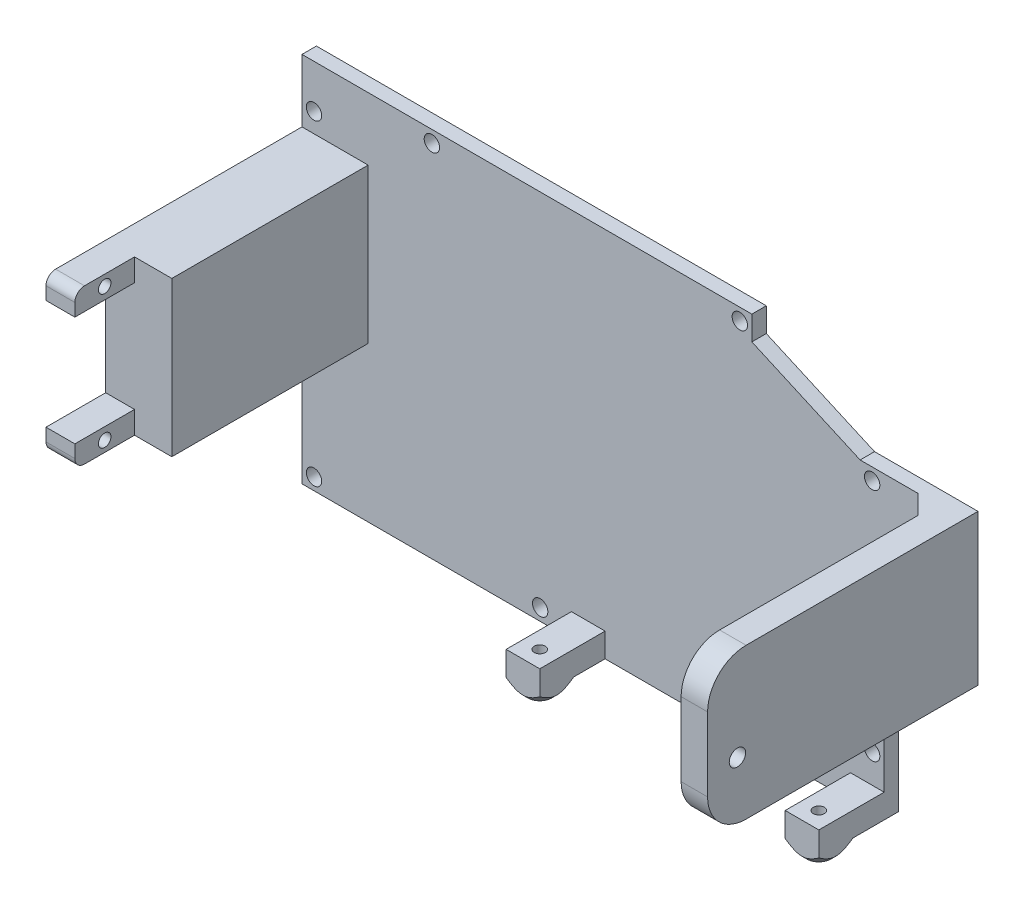
SolidWorks part; units mm, degrees
material "Nylon 101 70%"
ref_plane "Front Plane" through (0, 0, 0) normal (0, 0, 1) x (1, 0, 0)
ref_plane "Top Plane" through (0, 0, 0) normal (0, 1, 0) x (1, 0, 0)
ref_plane "Right Plane" through (0, 0, 0) normal (1, 0, 0) x (0, 0, -1)
sketch "Sketch19" plane through (0, 0, 0) normal (0, 0, 1) x (1, 0, 0)
  line L10 (-54.5, -38) -> (-54.5, 29.3)
  line L11 (56.5, -38) -> (-54.5, -38)
  line L12 (56.5, 19.3) -> (56.5, -38)
  line L13 (61.5, 19.3) -> (56.5, 19.3)
  line L14 (61.5, -43) -> (61.5, 19.3)
  line L15 (-59.5, -43) -> (61.5, -43)
  line L16 (-59.5, 34.3) -> (-59.5, -43)
  line L17 (34, 34.3) -> (-59.5, 34.3)
  line L18 (34, 29.3) -> (34, 34.3)
  line L19 (-54.5, 29.3) -> (34, 29.3)
  line L20 (-54.5, -38) -> (-54.5, 29.3) construction
  line L21 (56.5, -38) -> (-54.5, -38) construction
  line L22 (56.5, 19.3) -> (56.5, -38) construction
  line L23 (61.5, 19.3) -> (56.5, 19.3)
  line L24 (61.5, -43) -> (61.5, 19.3)
  line L25 (-59.5, -43) -> (61.5, -43)
  line L26 (-59.5, 34.3) -> (-59.5, -43)
  line L27 (34, 34.3) -> (-59.5, 34.3)
  line L28 (34, 29.3) -> (34, 34.3)
  line L29 (-54.5, 29.3) -> (34, 29.3) construction
  line L40 (34, 29.3) -> (56.5, 19.3)
  dimension "D1" = 0
extrude "Base" add sketch "Sketch19" along normal blind 3
ref_plane "Top" through (0, 0, 3) normal (0, 0, 1) x (1, 0, 0)
sketch "Sketch20" plane through (0, 0, 0) normal (0, 0, 1) x (1, 0, 0)
  line L0 (-55.6482, 16.7928) -> (-55.6482, 21.05) construction
  line L1 (-55.4482, -7.9314) -> (-55.4482, -9.2765) construction
  line L2 (-55.8482, -6.2) -> (-73.6482, -6.2) construction
  line L3 (-55.8482, -6.2) -> (-73.6482, -6.2) construction
  line L4 (-55.6482, 16.7928) -> (-55.6482, 21.05) construction
  line L5 (-55.4482, -7.9314) -> (-55.4482, -9.2765) construction
  line L6 (-55.8482, 16.6) -> (-73.6482, 16.6) construction
  line L7 (-55.8482, 16.6) -> (-73.6482, 16.6) construction
  line L8 (-55.6482, -10.65) -> (-55.6482, -6.3928) construction
  line L9 (-55.4482, 21.25) -> (-53.2982, 21.25) construction
  line L10 (-55.4482, 18.2177) -> (-55.4482, 19.799) construction
  line L11 (-55.4482, 18.2177) -> (-55.4482, 19.799) construction
  line L12 (-53.2982, -10.85) -> (-55.4482, -10.85) construction
  line L13 (-53.2982, -10.85) -> (-55.4482, -10.85)
  line L14 (-55.4482, 21.25) -> (-53.2982, 21.25)
  line L15 (-51.3482, -6.2) -> (-52.8982, -6.2) construction
  line L16 (-51.3482, -6.2) -> (-52.8982, -6.2) construction
  line L17 (-52.8982, 16.6) -> (-51.3482, 16.6) construction
  line L18 (-52.8982, 16.6) -> (-51.3482, 16.6) construction
  line L19 (-45.7482, 8.6095) -> (-50.9482, 8.6095) construction
  line L20 (-45.7482, 8.6095) -> (-50.9482, 8.6095) construction
  line L21 (-50.9482, -6.2) -> (-45.3482, -6.2) construction
  line L22 (-50.9482, -6.2) -> (-45.3482, -6.2) construction
  line L23 (-53.2982, 21.25) -> (-45.7482, 21.25)
  line L24 (-45.7482, 21.25) -> (-45.7482, 8.6095)
  line L25 (-45.7482, 8.6095) -> (-45.7482, -10.85)
  line L26 (-45.7482, -10.85) -> (-53.2982, -10.85)
  line L27 (-55.4482, 21.25) -> (-59.5, 21.25)
  line L28 (-59.5, 34.3) -> (-59.5, -43) construction
  line L29 (-59.5, 21.25) -> (-59.5, -10.85)
  line L30 (-59.5, -10.85) -> (-55.4482, -10.85)
  line L31 (-55.6482, -10.65) -> (-55.6482, -6.3928) construction
extrude "Servo support" add sketch "Sketch20" along normal up to surface (43.8 mm away)
sketch "Sketch21" plane through (0, 0, 43.8) normal (0, 0, 1) x (1, 0, 0)
  line L0 (-53.5, -6.3928) -> (-53.5, -10.65) construction
  line L2 (-53.5, -6.2) -> (-53.5, -10.85)
  line L4 (-55.8482, -6.2) -> (-73.6482, -6.2) construction
  line L5 (-53.5, -6.2) -> (-59.5, -6.2)
  line L6 (-55.8482, 16.6) -> (-73.6482, 16.6) construction
  line L7 (-53.5, 16.6) -> (-59.5, 16.6)
  line L8 (-59.5, -10.85) -> (-55.4482, -10.85) construction
  line L9 (-59.5, -10.85) -> (-53.5, -10.85)
  line L10 (-55.4482, 21.25) -> (-59.5, 21.25) construction
  line L11 (-53.5, 21.25) -> (-59.5, 21.25)
  line L20 (-59.5, 21.25) -> (-59.5, -10.85) construction
  line L21 (-59.5, 21.25) -> (-59.5, 16.6)
  line L22 (-59.5, -6.2) -> (-59.5, -10.85)
  line L25 (-53.5, -6.2) -> (-53.5, 16.6) construction
  line L27 (-45.7482, 21.25) -> (-59.5, 21.25) construction
  line L28 (-59.5, -10.85) -> (-45.7482, -10.85) construction
  line L29 (-53.5, 16.6) -> (-53.5, 21.25)
extrude "Servo mounts" add sketch "Sketch21" along normal up to surface (12.4 mm away)
sketch "Sketch22" plane through (-59.5, 0, 0) normal (-1, 0, 0) x (0, 0, 1)
  arc A7 (50.352, -9.2765) -> (49.648, -9.2765) centre (50, -8.65) ccw construction
  arc A8 (50.352, -9.2765) -> (49.648, -9.2765) centre (50, -8.65) ccw construction
  arc A9 (49.6372, 19.799) -> (50.3628, 19.799) centre (50, 19.05) ccw construction
  arc A10 (49.6372, 19.799) -> (50.3628, 19.799) centre (50, 19.05) ccw construction
  circle A11 centre (50, -8.65) radius 1.3
  circle A12 centre (50, 19.05) radius 1.3
  dimension "D2" = 2.6
extrude "Servo screws" cut sketch "Sketch22" against normal up to next
fillet "Fillet1" radius 2 2 edges at (-56.5, -10.85, 56.2) (-56.5, 21.25, 56.2)
sketch "Sketch23" plane through (0, 0, 0) normal (0, 0, 1) x (1, 0, 0)
  line L0 (72, -14.6) -> (72, 14.6) construction
  line L2 (61.5, -12) -> (78, -12)
  line L3 (61.5, -43) -> (61.5, 19.3) construction
  line L4 (78, -12) -> (78, 19.3)
  line L5 (61.5, 19.3) -> (78, 19.3)
  line L6 (61.5, 19.3) -> (61.5, -12)
  line L9 (72, -14.6) -> (72, 14.6) construction
  point P0 (72, 0)
  dimension "D1" = 6
  dimension "D2" = 12
extrude "Shaft support" add sketch "Sketch23" along normal up to surface (3 mm away) up to plane "Top"
sketch "Sketch24" plane through (0, 0, 0) normal (0, 0, 1) x (1, 0, 0)
  line L0 (78, -12) -> (78, 19.3) construction
  line L1 (78, -12) -> (78, 19.3)
  line L2 (61.5, 19.3) -> (78, 19.3) construction
  line L3 (72.5, 19.3) -> (78, 19.3)
  line L4 (61.5, -12) -> (78, -12) construction
  line L5 (72.5, -12) -> (78, -12)
  line L6 (72.5, 19.3) -> (72.5, -12)
  line L10 (72, -14.6) -> (72, 14.6) construction
  dimension "D1" = 0.5
extrude "Boss-Extrude6" add sketch "Sketch24" along normal up to surface (56.2 mm away) up to face at (-56.5, -7.525, 56.2)
fillet "Fillet2" radius 8 1 edges at (61.5, -12, 1.5)
fillet "Fillet3" radius 8 2 edges at (75.25, 19.3, 56.2) (75.25, -12, 56.2)
sketch "Sketch25" plane through (72.5, 0, 0) normal (-1, 0, 0) x (0, 0, 1)
  circle A3 centre (50, 0) radius 1.4 construction
  circle A4 centre (50, 0) radius 1.4 construction
  circle A5 centre (50, 0) radius 1.7
  dimension "D2" = 3.4
extrude "Shaft" cut sketch "Sketch25" against normal up to next
sketch "Sketch26" plane through (0, 0, 0) normal (0, 0, 1) x (1, 0, 0)
  circle A5 centre (-57, 25.3) radius 1.4
  circle A6 centre (-57, 25.3) radius 1.4 construction
  circle A7 centre (-10, -40.5) radius 1.4
  circle A8 centre (-10, -40.5) radius 1.4 construction
  circle A9 centre (59, -32) radius 1.4
  circle A10 centre (59, -32) radius 1.4 construction
  circle A13 centre (59, 16.8) radius 1.4
  circle A14 centre (59, 16.8) radius 1.4 construction
  circle A15 centre (31.5, 31.8) radius 1.4
  circle A16 centre (31.5, 31.8) radius 1.4 construction
  circle A19 centre (-32.5, 31.8) radius 1.4
  circle A20 centre (-32.5, 31.8) radius 1.4 construction
  circle A21 centre (-57, -40.5) radius 1.4
  circle A22 centre (-57, -40.5) radius 1.4 construction
  circle A44 centre (-57, -40.5) radius 1.6
  circle A46 centre (-10, -40.5) radius 1.6
  circle A47 centre (59, -32) radius 1.6
  circle A49 centre (59, 16.8) radius 1.6
  circle A50 centre (31.5, 31.8) radius 1.6
  circle A52 centre (-32.5, 31.8) radius 1.6
  circle A53 centre (-57, 25.3) radius 1.6
  circle A63 centre (-57, -14.5) radius 1.4 construction
  circle A64 centre (-57, -14.5) radius 1.4
  circle A112 centre (45.5, -40.5) radius 1.4 construction
  circle A113 centre (45.5, -40.5) radius 1.4
  dimension "D2" = 3.2
  dimension "D3" = 0
  dimension "D4" = 0
  dimension "D5" = 0
  dimension "D7" = 0
  dimension "D8" = 0
  dimension "D10" = 0
  dimension "D11" = 0
extrude "Screws" cut sketch "Sketch26" along normal up to next
sketch "Sketch30" plane through (0, -43, 0) normal (0, -1, 0) x (1, 0, 0)
  circle A1 centre (0, 13.0765) radius 1.35
  circle A2 centre (0, 13.0765) radius 1.35 construction
  circle A3 centre (58, 13.0765) radius 1.35
  circle A4 centre (58, 13.0765) radius 1.35 construction
  circle A10 centre (0, 13.0765) radius 2.5
  circle A11 centre (58, 13.0765) radius 2.5
  dimension "D3" = 5
  dimension "D1" = 0
  dimension "D2" = 0
sketch "Sketch31" plane through (0, -43, 0) normal (0, -1, 0) x (1, 0, 0)
  line L0 (-59.5, 3) -> (61.5, 3) construction
  line L1 (-3.5, 3) -> (3.5, 3)
  line L2 (-3.5, 3) -> (-3.5, 16.5765)
  line L3 (-3.5, 16.5765) -> (3.5, 16.5765)
  line L4 (3.5, 16.5765) -> (3.5, 3)
  line L5 (54.5, 3) -> (54.5, 16.5765)
  line L6 (54.5, 16.5765) -> (61.5, 16.5765)
  line L7 (61.5, 3) -> (61.5, 16.5765)
  line L9 (0, 13.0765) -> (0, 16.5765) construction
  line L10 (58, 13.0765) -> (58, 16.5765) construction
  line L11 (54.5, 3) -> (61.5, 3)
  dimension "D1" = 7
  dimension "D2" = 3.5
extrude "Boss-Extrude8" add sketch "Sketch31" against normal blind 5
extrude "Boss-Extrude9" add sketch "Sketch30" along normal blind 2.5
sketch "Sketch32" plane through (0, -38, 0) normal (0, 1, 0) x (1, 0, 0)
  circle A0 centre (0, -13.0765) radius 1.15
  circle A1 centre (58, -13.0765) radius 1.15
  dimension "D1" = 2.3
extrude "Cut-Extrude1" cut sketch "Sketch32" against normal up to next
chamfer "Chamfer1" distance 2.5 angle 45 2 edges at (55.5, -43, 13.0765) (-2.5, -43, 13.0765)
chamfer "Chamfer2" distance 4 angle 45 1 edges at (72.5, 3.65, 3)
